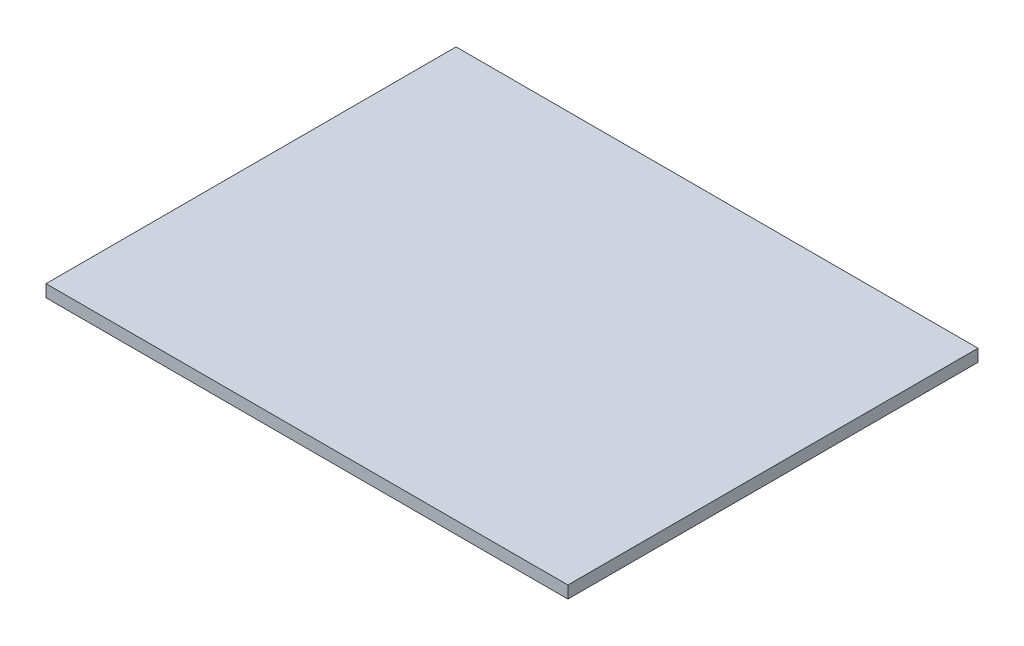
SolidWorks part; units mm, degrees
material "Acrylic (Medium-high impact)"
ref_plane "Front Plane" through (0, 0, 0) normal (0, 0, 1) x (1, 0, 0)
ref_plane "Top Plane" through (0, 0, 0) normal (0, 1, 0) x (1, 0, 0)
ref_plane "Right Plane" through (0, 0, 0) normal (1, 0, 0) x (0, 0, -1)
sketch "Sketch1" plane through (0, 0, 0) normal (0, 1, 0) x (1, 0, 0)
  line L1 (-135.35, 106.35) -> (135.35, 106.35)
  line L2 (-135.35, 106.35) -> (-135.35, -106.35)
  line L3 (-135.35, -106.35) -> (135.35, -106.35)
  line L4 (135.35, 106.35) -> (135.35, -106.35)
  line L5 (-135.35, 106.35) -> (135.35, -106.35) construction
  line L6 (-135.35, -106.35) -> (135.35, 106.35) construction
  point P0 (0, 0)
  dimension "D1" = 212.7
  dimension "D2" = 270.7
extrude "Boss-Extrude1" add sketch "Sketch1" along normal blind 6.35
